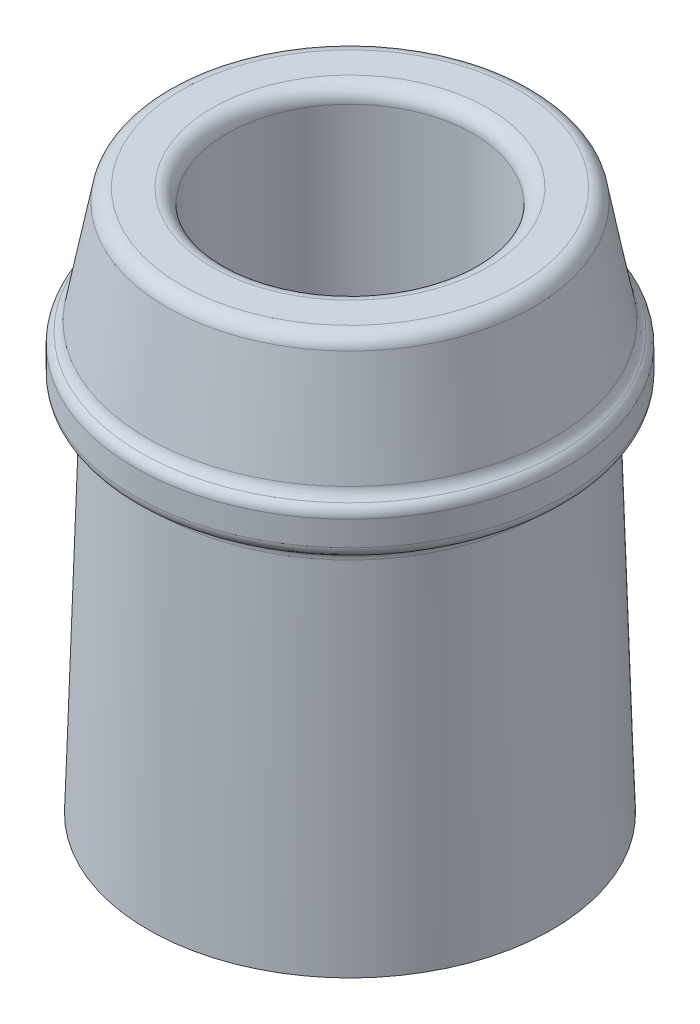
SolidWorks part; units mm, degrees
ref_plane "Front Plane" through (0, 0, 0) normal (0, 0, 1) x (1, 0, 0)
ref_plane "Top Plane" through (0, 0, 0) normal (0, 1, 0) x (1, 0, 0)
ref_plane "Right Plane" through (0, 0, 0) normal (1, 0, 0) x (0, 0, -1)
sketch "Sketch1" plane through (0, 0, 0) normal (0, 0, 1) x (1, 0, 0)
  line L0 (0, 0) -> (0, 17.7282) construction
  line L1 (5, 22) -> (5, 0)
  line L6 (8.2, 0) -> (7.75, 15)
  line L7 (7.75, 15) -> (8.725, 15)
  line L8 (8.725, 15) -> (8.725, 17)
  line L9 (8.725, 17) -> (8.3, 17)
  line L10 (8.3, 17) -> (7.35, 22)
  line L11 (7.35, 22) -> (5, 22)
  line L12 (0, 0) -> (18.4734, 0) construction
  line L13 (8.2, 0) -> (5, 0)
  point P5 (7.75, 12.0754)
  dimension "D1" = 7.35
  dimension "D2" = 5
  dimension "D3" = 5
  dimension "D4" = 0.95
  dimension "D5" = 8.725
  dimension "D6" = 7.75
  dimension "D7" = 22
  dimension "D8" = 8.2
  dimension "D9" = 2
revolve "Revolve1" add sketch "Sketch1" angle 360 about L0
fillet "Fillet1" radius 0.5 2 edges at (0, 15, -8.725) (0, 17, -8.725)
fillet "Fillet2" radius 0.6 4 edges at (0, 15, -7.75) (0, 17, -8.3) (0, 22, -5) (0, 22, -7.35)
